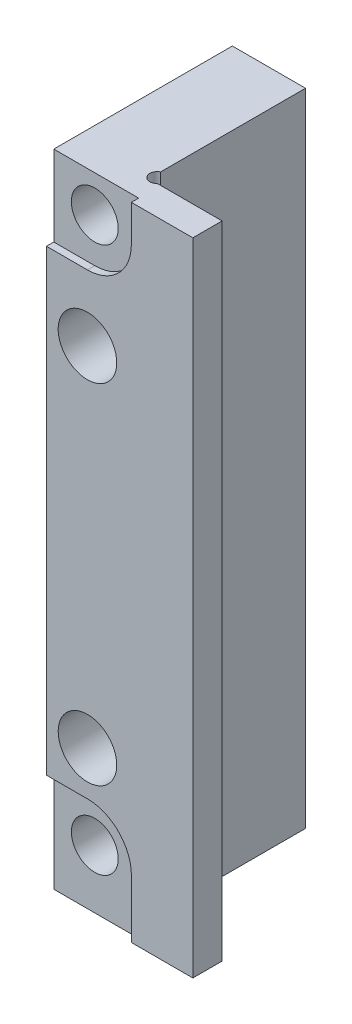
SolidWorks part; units mm, degrees
ref_plane "前基準面" through (0, 0, 0) normal (0, 0, 1) x (1, 0, 0)
ref_plane "上基準面" through (0, 0, 0) normal (0, 1, 0) x (1, 0, 0)
ref_plane "右基準面" through (0, 0, 0) normal (1, 0, 0) x (0, 0, -1)
sketch "草圖1" plane through (0, 0, 0) normal (0, 0, 1) x (1, 0, 0)
  line L0 (-29.9, 26.9) -> (-29.9, -26.9) construction
  line L1 (-38, 30) -> (38, 30) construction
  line L2 (-38, 30) -> (-38, -30) construction
  line L3 (-38, -30) -> (38, -30) construction
  line L4 (38, 30) -> (38, -30) construction
  line L5 (-38, 30) -> (38, -30) construction
  line L6 (-38, -30) -> (38, 30) construction
  line L7 (-29.9, 26.9) -> (29.9, 26.9) construction
  line L8 (-34.9, 21.9) -> (-34.9, -21.9) construction
  line L9 (-29.9, -26.9) -> (29.9, -26.9) construction
  line L10 (34.9, 21.9) -> (34.9, -21.9) construction
  line L11 (-34.9, 26.9) -> (34.9, -26.9) construction
  line L12 (-34.9, -26.9) -> (34.9, 26.9) construction
  line L13 (-34.9, 21.9) -> (-24.9, 21.9)
  line L14 (-24.9, 21.9) -> (-24.9, -21.9)
  line L15 (-24.9, -21.9) -> (-34.9, -21.9)
  line L16 (-34.9, 21.9) -> (-34.9, -21.9)
  arc A0 (29.9, -26.9) -> (34.9, -21.9) centre (29.9, -21.9) ccw construction
  arc A1 (29.9, 26.9) -> (34.9, 21.9) centre (29.9, 21.9) cw construction
  arc A2 (-34.9, -21.9) -> (-29.9, -26.9) centre (-29.9, -21.9) ccw construction
  arc A3 (-29.9, 26.9) -> (-34.9, 21.9) centre (-29.9, 21.9) ccw construction
  point P0 (0, 0)
  point P6 (0, 0)
  dimension "D5" = 5
  dimension "D1" = 76
  dimension "D2" = 60
  dimension "D3" = 3.1
  dimension "D4" = 3.1
  dimension "D6" = 5
  dimension "D7" = 10
extrude "填料-伸長1" add sketch "草圖1" against normal blind 10
sketch "草圖2" plane through (0, -21.9, 0) normal (0, -1, 0) x (1, 0, 0)
  line L0 (-24.9, -10) -> (-24.9, -2)
  line L1 (-24.9, -10) -> (-24.9, 0) construction
  line L2 (-24.9, -2) -> (-29.9, -2)
  line L3 (-29.9, -2) -> (-29.9, -10)
  line L4 (-34.9, -10) -> (-24.9, -10) construction
  line L5 (-29.9, -10) -> (-24.9, -10)
  line L6 (-27.4, -2) -> (-27.4, -10) construction
  line L7 (-29.9, -6) -> (-24.9, -6) construction
  line L8 (-27.4, -6) -> (-29.9, -2) construction
  circle A0 centre (-29.684, -2.3456) radius 0.5
  line M6 (-24.9, -10) -> (-24.9, 0)
  dimension "D3" = 1
  dimension "D4" = 0.3456
  dimension "D1" = 8
  dimension "D2" = 5
extrude "除料-伸長1" cut sketch "草圖2" against normal through all contours L3 A0 L2 | L3 L5 L2 A0 M6 | A0 region at (-27.3706, -21.9, -6.0487) region at (-29.5737, -21.9, -2.3984)
sketch "草圖3" plane through (0, 0, 0) normal (0, 0, 1) x (1, 0, 0)
  line L0 (-34.9, -21.9) -> (-24.9, -21.9) construction
  line L1 (-34.9, 21.9) -> (-34.9, -21.9) construction
  line L2 (-24.9, 21.9) -> (-34.9, 21.9) construction
  circle A0 centre (-32.1, -17.9) radius 1.6
  circle A1 centre (-32.1, 19.4) radius 1.6
  dimension "D1" = 3.2
  dimension "D4" = 3.2
  dimension "D2" = 4
  dimension "D3" = 2.8
  dimension "D5" = 2.5
  dimension "D6" = 2.8
extrude "除料-伸長2" cut sketch "草圖3" against normal through all
sketch "草圖4" plane through (0, 0, 0) normal (0, 0, 1) x (1, 0, 0)
  line L0 (-34.9, 21.9) -> (-34.9, -21.9) construction
  line L1 (-24.9, 21.9) -> (-34.9, 21.9) construction
  line L2 (-34.9, 0) -> (-24.9, 0) construction
  line L3 (-24.9, -21.9) -> (-24.9, 21.9) construction
  circle A0 centre (-32.1, 11.9) radius 2
  circle A1 centre (-32.1, -11.9) radius 2
  dimension "D1" = 2.8
  dimension "D3" = 4
  dimension "D2" = 10
extrude "除料-伸長3" cut sketch "草圖4" against normal through all
sketch "草圖5" plane through (0, 0, 0) normal (0, 0, 1) x (1, 0, 0)
  line L0 (-29.1, 19.4) -> (-29.1, 21.9)
  line L1 (-24.9, 21.9) -> (-34.9, 21.9) construction
  line L2 (-32.1, 16.4) -> (-34.9, 16.4)
  line L3 (-34.9, 21.9) -> (-34.9, -21.9) construction
  line L4 (-34.9, 16.4) -> (-34.9, 21.9)
  line L5 (-34.9, 21.9) -> (-29.1, 21.9)
  line L6 (-32.1, -14.9) -> (-34.9, -14.9)
  line L7 (-29.1, -17.9) -> (-29.1, -21.9)
  line L10 (-29.1, -21.9) -> (-34.9, -21.9)
  line L11 (-34.9, -21.9) -> (-34.9, -14.9)
  circle A0 centre (-32.1, 19.4) radius 3 construction
  arc A1 (-29.1, 19.4) -> (-32.1, 16.4) centre (-32.1, 19.4) cw
  circle A2 centre (-32.1, -17.9) radius 3 construction
  arc A3 (-32.1, -14.9) -> (-29.1, -17.9) centre (-32.1, -17.9) cw
  circle A4 centre (-32.1, -11.9) radius 2 construction
  dimension "D1" = 6
  dimension "D2" = 6
  dimension "D3" = 6
extrude "除料-伸長4" cut sketch "草圖5" against normal blind 0.5
sketch "草圖6" plane through (0, 0, -10) normal (0, 0, -1) x (-1, 0, 0)
  line L4 (29.9, 21.9) -> (29.9, -21.9)
  line L5 (29.9, -21.9) -> (34.9, -21.9)
  line L6 (34.9, -21.9) -> (34.9, 21.9)
  line L7 (34.9, 21.9) -> (29.9, 21.9)
  line L8 (29.9, 21.9) -> (29.9, -21.9)
  line L9 (29.9, -21.9) -> (34.9, -21.9)
  line L10 (34.9, -21.9) -> (34.9, 21.9)
  line L11 (34.9, 21.9) -> (29.9, 21.9)
  circle A1 centre (32.1, 11.9) radius 2
  circle A2 centre (32.1, 11.9) radius 2
  circle A3 centre (32.1, -11.9) radius 2
  circle A4 centre (32.1, -11.9) radius 2
  circle A5 centre (32.1, -17.9) radius 1.6
  circle A6 centre (32.1, -17.9) radius 1.6
  circle A7 centre (32.1, 19.4) radius 1.6
  circle A8 centre (32.1, 19.4) radius 1.6
  dimension "D1" = 0
  dimension "D2" = 0
  dimension "D3" = 0
  dimension "D4" = 0
  dimension "D5" = 0
extrude "填料-伸長2" add sketch "草圖6" along normal blind 2.7
